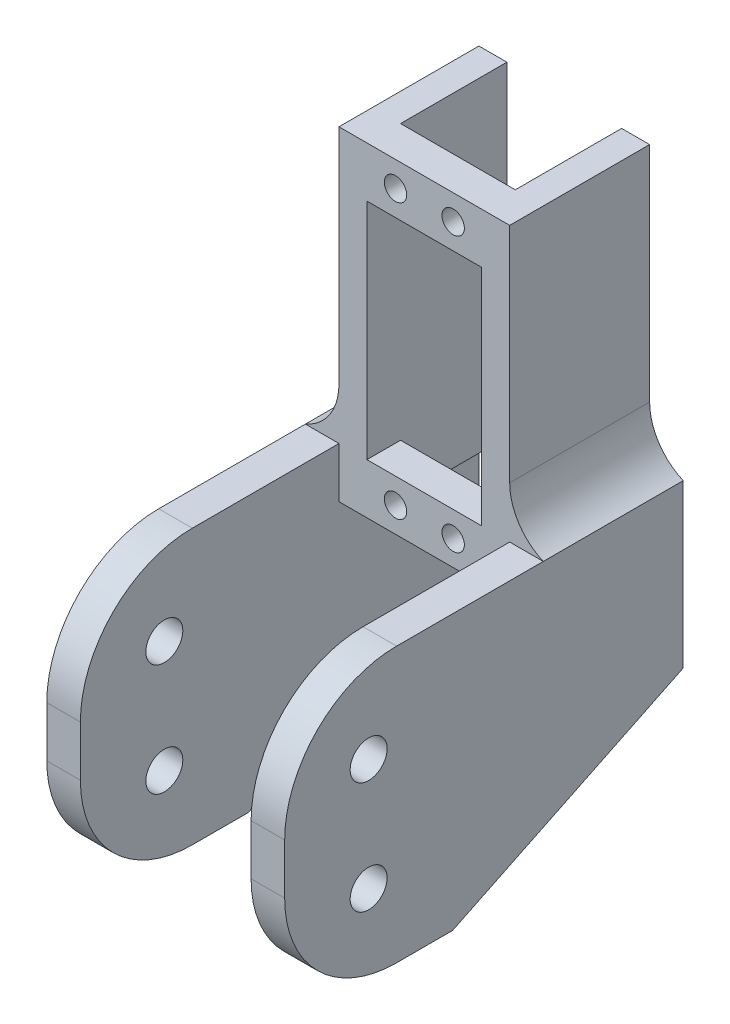
SolidWorks part; units mm, degrees
ref_plane "Front Plane" through (0, 0, 0) normal (0, 0, 1) x (1, 0, 0)
ref_plane "Top Plane" through (0, 0, 0) normal (0, 1, 0) x (1, 0, 0)
ref_plane "Right Plane" through (0, 0, 0) normal (1, 0, 0) x (0, 0, -1)
sketch "Sketch1" plane through (0, 0, 0) normal (0, 0, 1) x (1, 0, 0)
  line L1 (0, 0) -> (20.5, 0)
  line L2 (0, 0) -> (0, 9)
  line L3 (0, 9) -> (20.5, 9)
  line L4 (20.5, 0) -> (20.5, 9)
  dimension "D1" = 20.5
  dimension "D2" = 9
extrude "Boss-Extrude1" add sketch "Sketch1" along normal blind 6
sketch "Sketch2" plane through (20.5, 0, 0) normal (1, 0, 0) x (0, 0, -1)
  line L1 (-6, 9) -> (19, 9)
  line L2 (-6, 9) -> (-6, -49)
  line L3 (-6, -49) -> (19, -49)
  line L4 (19, 9) -> (19, -49)
  dimension "D1" = 25
  dimension "D2" = 58
extrude "Boss-Extrude2" add sketch "Sketch2" along normal blind 5
pattern_linear "LPattern1" count 2 spacing 49 along (0, -1, 0) of "Boss-Extrude1"
pattern_linear "LPattern2" count 2 spacing 25.5 along (-1, 0, 0) of "Boss-Extrude2"
sketch "Sketch3" plane through (0, 0, 6) normal (0, 0, 1) x (1, 0, 0)
  line L0 (0, 0) -> (20.5, 0) construction
  line L1 (25.5, 9) -> (-5, 9) construction
  circle A0 centre (5.1, 4.5) radius 2
  point P4 (10.25, 0)
  dimension "D2" = 4
  dimension "D1" = 5.15
  dimension "D3" = 4.5
extrude "Cut-Extrude1" cut sketch "Sketch3" against normal up to next
pattern_linear "LPattern3" count 2 spacing 10.3 along (1, 0, 0) count 2 spacing 49 along (0, -1, 0) of "Cut-Extrude1"
sketch "Sketch4" plane through (25.5, 0, 0) normal (1, 0, 0) x (0, 0, -1)
  line L0 (-6, 9) -> (-6, -49) construction
  line L1 (-6, -40) -> (19, -40)
  line L2 (-6, -40) -> (-6, -69)
  line L3 (-6, -69) -> (19, -69)
  line L4 (19, -40) -> (19, -69)
  line L5 (19, -49) -> (19, 9) construction
  line L6 (-6, -49) -> (19, -49) construction
  dimension "D1" = 0
  dimension "D2" = 0
  dimension "D3" = 20
extrude "Boss-Extrude3" add sketch "Sketch4" along normal blind 6
pattern_linear "LPattern4" count 2 spacing 36.5 along (-1, 0, 0) of "Boss-Extrude3"
sketch "Sketch6" plane through (0, 0, 6) normal (0, 0, 1) x (1, 0, 0)
  line L1 (31.5, -40) -> (25.5, -40)
  line L2 (31.5, -40) -> (31.5, -69)
  line L3 (31.5, -69) -> (25.5, -69)
  line L4 (25.5, -40) -> (25.5, -69)
  line L5 (-11, -40) -> (-5, -40)
  line L6 (-11, -40) -> (-11, -69)
  line L7 (-11, -69) -> (-5, -69)
  line L8 (-5, -40) -> (-5, -69)
extrude "Boss-Extrude5" add sketch "Sketch6" along normal blind 46.2
fillet "Fillet1" radius 10 2 edges at (25.5, -40, -6.5) (-5, -40, -6.5)
hole_wizard "M6 Clearance Hole1" positions "Sketch7" profile "Sketch8" hole size "M6" standard "ANSI Metric" end condition through all
sketch "Sketch7" plane through (-11, 0, 0) normal (-1, 0, 0) x (0, 0, 1)
  line L0 (52.2, -40) -> (52.2, -69) construction
  line L1 (6, -40) -> (52.2, -40) construction
  point P0 (37.2, -55)
  dimension "D1" = 15
  dimension "D2" = 15
sketch "Sketch8" plane through (-11, -55, 37.2) normal (0, 1, 0) x (0, 0, 1)
  line L0 (0, 0) -> (0, 42.5)
  line L1 (0, 42.5) -> (3.3, 42.5)
  line L2 (3.3, 42.5) -> (3.3, 0)
  line L5 (3.3, 0) -> (0, 0)
  line L11 (0, -6.35) -> (0, 107.95) construction
  dimension "Thru Hole Dia." = 6.6
  dimension "Thru Hole Depth" = 42.5
sketch "Sketch9" plane through (0, -69, 0) normal (0, -1, 0) x (1, 0, 0)
  line L0 (25.5, 52.2) -> (25.5, -19) construction
  line L1 (31.5, 52.2) -> (25.5, 52.2)
  line L2 (31.5, 52.2) -> (31.5, 22.2)
  line L3 (31.5, 22.2) -> (25.5, 22.2)
  line L4 (25.5, 52.2) -> (25.5, 22.2)
  line L5 (-11, 52.2) -> (-11, -19) construction
  line L6 (-5, 52.2) -> (-11, 52.2)
  line L7 (-5, 52.2) -> (-5, 22.2)
  line L8 (-5, 22.2) -> (-11, 22.2)
  line L9 (-11, 52.2) -> (-11, 22.2)
  dimension "D1" = 30
  dimension "D2" = 30
extrude "Boss-Extrude6" add sketch "Sketch9" along normal blind 20
sketch "Sketch10" plane through (31.5, 0, 0) normal (1, 0, 0) x (0, 0, -1)
  line L0 (-22.2, -89) -> (19, -69)
  line L1 (19, -69) -> (-19.8982, -69)
  line L2 (-19.8982, -69) -> (-23.8579, -89)
  line L3 (-22.2, -89) -> (-52.2, -89) construction
  line L11 (19, -40) -> (-6, -40)
  line L12 (-6, -40) -> (-52.2, -40)
  line L13 (-52.2, -40) -> (-52.2, -89)
  line L14 (-52.2, -89) -> (-22.2, -89)
  line L15 (-22.2, -89) -> (-22.2, -69)
  line L16 (-22.2, -69) -> (19, -69)
  line L17 (19, -69) -> (19, -40)
  line L18 (19, -40) -> (-6, -40)
  line L19 (-6, -40) -> (-52.2, -40)
  line L20 (-52.2, -40) -> (-52.2, -89)
  line L21 (-52.2, -89) -> (-23.8579, -89)
  line L22 (-22.2, -89) -> (-22.2, -69)
  line L23 (-22.2, -69) -> (19, -69)
  line L24 (19, -69) -> (19, -40)
  line M6 (-22.2, -89) -> (-22.2, -69)
  line M7 (-22.2, -69) -> (19, -69)
  dimension "D1" = 0
extrude "Boss-Extrude7" add sketch "Sketch10" against normal blind 6 contours L2 L0 M7 M6 | L2 M7 M6 region at (31.5, -75.7604, 8.0314) region at (31.5, -72.8754, 21.4327)
pattern_linear "LPattern5" count 2 spacing 36.5 along (-1, 0, 0) of "Boss-Extrude7"
fillet "Fillet2" radius 20 4 edges at (-8, -89, 52.2) (28.5, -89, 52.2) (28.5, -40, 52.2) (-8, -40, 52.2)
hole_wizard "M6 Clearance Hole2" positions "Sketch11" profile "Sketch12" hole size "M6" standard "ANSI Metric" end condition through all
sketch "Sketch11" plane through (31.5, 0, 0) normal (1, 0, 0) x (0, 0, -1)
  circle A0 centre (-37.2, -55) radius 3.3 construction
  point P0 (-37.2, -75)
  dimension "D1" = 0
  dimension "D2" = 20
sketch "Sketch12" plane through (31.5, -75, 37.2) normal (0, 1, 0) x (0, 0, -1)
  line L0 (0, 0) -> (0, 42.5)
  line L1 (0, 42.5) -> (3.3, 42.5)
  line L2 (3.3, 42.5) -> (3.3, 0)
  line L5 (3.3, 0) -> (0, 0)
  line L11 (0, -6.35) -> (0, 107.95) construction
  dimension "Thru Hole Dia." = 6.6
  dimension "Thru Hole Depth" = 42.5
